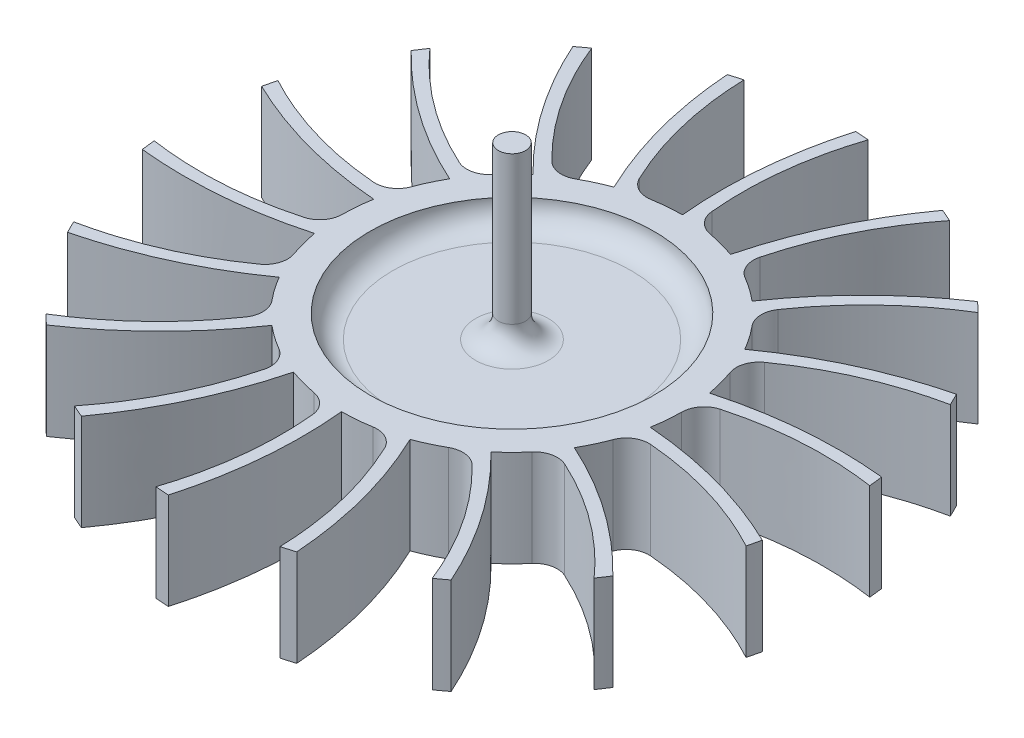
SolidWorks part; units mm, degrees
ref_plane "Front Plane" through (0, 0, 0) normal (0, 0, 1) x (1, 0, 0)
ref_plane "Top Plane" through (0, 0, 0) normal (0, 1, 0) x (1, 0, 0)
ref_plane "Right Plane" through (0, 0, 0) normal (1, 0, 0) x (0, 0, -1)
sketch "Sketch1" plane through (0, 0, 0) normal (0, 1, 0) x (1, 0, 0)
  circle A0 centre (0, 0) radius 36.83
  dimension "D1" = 73.66
extrude "Boss-Extrude1" add sketch "Sketch1" along normal blind 10.795
sketch "Sketch2" plane through (0, 10.795, 0) normal (0, 1, 0) x (1, 0, 0)
  circle A1 centre (0, 0) radius 15.875
  dimension "D2" = 31.75
extrude "Cut-Extrude1" cut sketch "Sketch2" against normal blind 2.54
sketch "Sketch3" plane through (0, 0, 0) normal (0, -1, 0) x (1, 0, 0)
  circle A0 centre (0, 0) radius 3.5
  dimension "D1" = 7
extrude "Cut-Extrude2" cut sketch "Sketch3" against normal blind 3
sketch "Sketch4" plane through (0, 10.795, 0) normal (0, 1, 0) x (1, 0, 0)
  circle A0 centre (0, 0) radius 19.05
  arc A1 (0, 19.05) -> (1.5635, 18.9857) centre (0, 0) cw
  arc A2 (3.1157, 36.698) -> (1.6104, 36.7948) centre (0, 0) ccw
  circle A3 centre (0, 0) radius 36.83 construction
  arc A4 (15.4792, 33.4192) -> (14.0978, 34.025) centre (0, 0) ccw
  arc A5 (6.5155, 17.9011) -> (7.9627, 17.306) centre (0, 0) cw
  arc A6 (25.9758, 26.1095) -> (24.8849, 27.1513) centre (0, 0) ccw
  arc A7 (12.2451, 14.5931) -> (13.4015, 13.5389) centre (0, 0) cw
  arc A8 (33.3392, 15.6507) -> (32.6704, 17.0027) centre (0, 0) ccw
  arc A9 (16.4978, 9.525) -> (17.2239, 8.1388) centre (0, 0) cw
  arc A10 (36.6815, 3.3042) -> (36.5154, 4.8034) centre (0, 0) ccw
  arc A11 (18.7606, 3.308) -> (18.9688, 1.7571) centre (0, 0) cw
  arc A12 (35.5994, -9.4409) -> (35.9561, -7.9753) centre (0, 0) ccw
  arc A13 (18.7606, -3.308) -> (18.4258, -4.8366) centre (0, 0) cw
  arc A14 (30.2235, -21.0473) -> (31.06, -19.792) centre (0, 0) ccw
  arc A15 (16.4978, -9.525) -> (15.6604, -10.8469) centre (0, 0) cw
  arc A16 (21.2022, -30.115) -> (22.4176, -29.2216) centre (0, 0) ccw
  arc A17 (12.2451, -14.5931) -> (11.0061, -15.5489) centre (0, 0) cw
  arc A18 (9.6236, -35.5504) -> (11.0713, -35.1266) centre (0, 0) ccw
  arc A19 (6.5155, -17.9011) -> (5.0243, -18.3755) centre (0, 0) cw
  arc A20 (-3.1157, -36.698) -> (-1.6104, -36.7948) centre (0, 0) ccw
  arc A21 (0, -19.05) -> (-1.5635, -18.9857) centre (0, 0) cw
  arc A22 (-15.4792, -33.4192) -> (-14.0978, -34.025) centre (0, 0) ccw
  arc A23 (-6.5155, -17.9011) -> (-7.9627, -17.306) centre (0, 0) cw
  arc A24 (-25.9758, -26.1095) -> (-24.8849, -27.1513) centre (0, 0) ccw
  arc A25 (-12.2451, -14.5931) -> (-13.4015, -13.5389) centre (0, 0) cw
  arc A26 (-33.3392, -15.6507) -> (-32.6704, -17.0027) centre (0, 0) ccw
  arc A27 (-16.4978, -9.525) -> (-17.2239, -8.1388) centre (0, 0) cw
  arc A28 (-36.6815, -3.3042) -> (-36.5154, -4.8034) centre (0, 0) ccw
  arc A29 (-18.7606, -3.308) -> (-18.9688, -1.7571) centre (0, 0) cw
  arc A30 (-35.5994, 9.4409) -> (-35.9561, 7.9753) centre (0, 0) ccw
  arc A31 (-18.7606, 3.308) -> (-18.4258, 4.8366) centre (0, 0) cw
  arc A32 (-30.2235, 21.0473) -> (-31.06, 19.792) centre (0, 0) ccw
  arc A33 (-16.4978, 9.525) -> (-15.6604, 10.8469) centre (0, 0) cw
  arc A34 (-21.2022, 30.115) -> (-22.4176, 29.2216) centre (0, 0) ccw
  arc A35 (-12.2451, 14.5931) -> (-11.0061, 15.5489) centre (0, 0) cw
  arc A36 (-9.6236, 35.5504) -> (-11.0713, 35.1266) centre (0, 0) ccw
  arc A37 (-6.5155, 17.9011) -> (-5.0243, 18.3755) centre (0, 0) cw
  spline S0 degree 2 poles (0, 19.05) (-0.8707, 28.0807) (1.6104, 36.7948) knots 0 0 0 1 1 1
  spline S1 degree 2 poles (1.5635, 18.9857) (0.2532, 28.0362) (3.1157, 36.698) knots 0 0 0 1 1 1
  spline S2 degree 2 poles (7.9627, 17.306) (9.8269, 26.2588) (15.4792, 33.4192) knots 0 0 0 1 1 1
  spline S3 degree 2 poles (6.5155, 17.9011) (8.786, 26.6851) (14.0978, 34.025) knots 0 0 0 1 1 1
  spline S4 degree 2 poles (13.4015, 13.5389) (18.2153, 21.3142) (25.9758, 26.1095) knots 0 0 0 1 1 1
  spline S5 degree 2 poles (12.2451, 14.5931) (17.3829, 22.0708) (24.8849, 27.1513) knots 0 0 0 1 1 1
  spline S6 degree 2 poles (17.2239, 8.1388) (24.4066, 13.7988) (33.3392, 15.6507) knots 0 0 0 1 1 1
  spline S7 degree 2 poles (16.4978, 9.525) (23.8833, 14.7944) (32.6704, 17.0027) knots 0 0 0 1 1 1
  spline S8 degree 2 poles (18.9688, 1.7571) (27.6542, 4.619) (36.6815, 3.3042) knots 0 0 0 1 1 1
  spline S9 degree 2 poles (18.7606, 3.308) (27.5029, 5.7337) (36.5154, 4.8034) knots 0 0 0 1 1 1
  spline S10 degree 2 poles (18.4258, -4.8366) (27.5662, -5.1178) (35.5994, -9.4409) knots 0 0 0 1 1 1
  spline S11 degree 2 poles (18.7606, -3.308) (27.8053, -4.0187) (35.9561, -7.9753) knots 0 0 0 1 1 1
  spline S12 degree 2 poles (15.6604, -10.8469) (24.1534, -14.2374) (30.2235, -21.0473) knots 0 0 0 1 1 1
  spline S13 degree 2 poles (16.4978, -9.525) (24.754, -13.2863) (31.06, -19.792) knots 0 0 0 1 1 1
  spline S14 degree 2 poles (11.0061, -15.5489) (17.8273, -21.6397) (21.2022, -30.115) knots 0 0 0 1 1 1
  spline S15 degree 2 poles (12.2451, -14.5931) (18.717, -20.9514) (22.4176, -29.2216) knots 0 0 0 1 1 1
  spline S16 degree 2 poles (5.0243, -18.3755) (9.351, -26.432) (9.6236, -35.5504) knots 0 0 0 1 1 1
  spline S17 degree 2 poles (6.5155, -17.9011) (10.4224, -26.0894) (11.0713, -35.1266) knots 0 0 0 1 1 1
  spline S18 degree 2 poles (-1.5635, -18.9857) (-0.2532, -28.0362) (-3.1157, -36.698) knots 0 0 0 1 1 1
  spline S19 degree 2 poles (0, -19.05) (0.8707, -28.0807) (-1.6104, -36.7948) knots 0 0 0 1 1 1
  spline S20 degree 2 poles (-7.9627, -17.306) (-9.8269, -26.2588) (-15.4792, -33.4192) knots 0 0 0 1 1 1
  spline S21 degree 2 poles (-6.5155, -17.9011) (-8.786, -26.6851) (-14.0978, -34.025) knots 0 0 0 1 1 1
  spline S22 degree 2 poles (-13.4015, -13.5389) (-18.2153, -21.3142) (-25.9758, -26.1095) knots 0 0 0 1 1 1
  spline S23 degree 2 poles (-12.2451, -14.5931) (-17.3829, -22.0708) (-24.8849, -27.1513) knots 0 0 0 1 1 1
  spline S24 degree 2 poles (-17.2239, -8.1388) (-24.4066, -13.7988) (-33.3392, -15.6507) knots 0 0 0 1 1 1
  spline S25 degree 2 poles (-16.4978, -9.525) (-23.8833, -14.7944) (-32.6704, -17.0027) knots 0 0 0 1 1 1
  spline S26 degree 2 poles (-18.9688, -1.7571) (-27.6542, -4.619) (-36.6815, -3.3042) knots 0 0 0 1 1 1
  spline S27 degree 2 poles (-18.7606, -3.308) (-27.5029, -5.7337) (-36.5154, -4.8034) knots 0 0 0 1 1 1
  spline S28 degree 2 poles (-18.4258, 4.8366) (-27.5662, 5.1178) (-35.5994, 9.4409) knots 0 0 0 1 1 1
  spline S29 degree 2 poles (-18.7606, 3.308) (-27.8053, 4.0187) (-35.9561, 7.9753) knots 0 0 0 1 1 1
  spline S30 degree 2 poles (-15.6604, 10.8469) (-24.1534, 14.2374) (-30.2235, 21.0473) knots 0 0 0 1 1 1
  spline S31 degree 2 poles (-16.4978, 9.525) (-24.754, 13.2863) (-31.06, 19.792) knots 0 0 0 1 1 1
  spline S32 degree 2 poles (-11.0061, 15.5489) (-17.8273, 21.6397) (-21.2022, 30.115) knots 0 0 0 1 1 1
  spline S33 degree 2 poles (-12.2451, 14.5931) (-18.717, 20.9514) (-22.4176, 29.2216) knots 0 0 0 1 1 1
  spline S34 degree 2 poles (-5.0243, 18.3755) (-9.351, 26.432) (-9.6236, 35.5504) knots 0 0 0 1 1 1
  spline S35 degree 2 poles (-6.5155, 17.9011) (-10.4224, 26.0894) (-11.0713, 35.1266) knots 0 0 0 1 1 1
  point P116 (0, 0)
  circle M7 centre (0, 0) radius 36.83
  dimension "D1" = 38.1
  dimension "D2" = 18
extrude "Cut-Extrude5" cut sketch "Sketch4" against normal through all contours S34 A0 S0 M7 | A0 S3 S1 M7 | A0 S5 S2 M7 | A0 S7 S4 M7 | A0 S9 S6 M7 | A0 S11 S8 M7 | A0 S13 S10 M7 | A0 S15 S12 M7 | A0 S17 S14 M7 | A0 S19 S16 M7 | A0 S21 S18 M7 | A0 S23 S20 M7 | A0 S25 S22 M7 | A0 S27 S24 M7 | A0 S29 S26 M7 | A0 S31 S28 M7 | A0 S33 S30 M7 | A0 S35 S32 M7 region at (28.9193, 10.795, 1.0358) region at (27.5295, 10.795, -8.9177) region at (26.821, 10.795, 10.8643) region at (22.8193, 10.795, -17.7956) region at (21.4877, 10.795, 19.3824) region at (15.3567, 10.795, -24.527) region at (13.5627, 10.795, 25.5628) region at (6.0418, 10.795, -28.3001) region at (4.0018, 10.795, 28.6598) region at (-4.0018, 10.795, -28.6598) region at (-6.0418, 10.795, 28.3001) region at (-13.5627, 10.795, -25.5628) region at (-15.3567, 10.795, 24.527) region at (-21.4877, 10.795, -19.3824) region at (-22.8193, 10.795, 17.7956) region at (-26.821, 10.795, -10.8643) region at (-27.5295, 10.795, 8.9177) region at (-28.9193, 10.795, -1.0358)
sketch "Sketch5" plane through (0, 8.255, 0) normal (0, 1, 0) x (1, 0, 0)
  circle A0 centre (0, 0) radius 1.524
  dimension "D1" = 3.048
extrude "Boss-Extrude2" add sketch "Sketch5" along normal blind 6.35
sketch "Sketch6" plane through (0, 0, 0) normal (0, -1, 0) x (-1, 0, 0)
  circle A0 centre (0, 0) radius 4.675
  circle A1 centre (0, 0) radius 12.7
  arc A2 (-18.9688, 1.7571) -> (-18.7606, -3.308) centre (0, 0) ccw construction
  dimension "D1" = 9.35
  dimension "D2" = 6.35
extrude "Cut-Extrude6" cut sketch "Sketch6" against normal blind 3.048
fillet "Fillet1" radius 2.54 18 edges at (11.0061, 5.3975, 15.5489) (5.0243, 5.3975, 18.3755) (-1.5635, 5.3975, 18.9857) (-7.9627, 5.3975, 17.306) (-13.4015, 5.3975, 13.5389) (-17.2239, 5.3975, 8.1388) (-18.9688, 5.3975, 1.7571) (-18.4258, 5.3975, -4.8366) (-15.6604, 5.3975, -10.8469) (-11.0061, 5.3975, -15.5489) (-5.0243, 5.3975, -18.3755) (1.5635, 5.3975, -18.9857) (7.9627, 5.3975, -17.306) (13.4015, 5.3975, -13.5389) (17.2239, 5.3975, -8.1388) (18.9688, 5.3975, -1.7571) (18.4258, 5.3975, 4.8366) (15.6604, 5.3975, 10.8469)
fillet "Fillet2" radius 2.54 2 edges at (0, 3.048, -12.7) (0, 8.255, 15.875)
fillet "Fillet3" radius 2.54 1 edges at (0, 3.048, -4.675)
sketch "Sketch7" plane through (0, 14.605, 0) normal (0, 1, 0) x (1, 0, 0)
  circle A0 centre (0, 0) radius 1.524
extrude "Boss-Extrude3" add sketch "Sketch7" along normal blind 12.7
fillet "Fillet4" radius 2.54 1 edges at (0, 8.255, 1.524)
